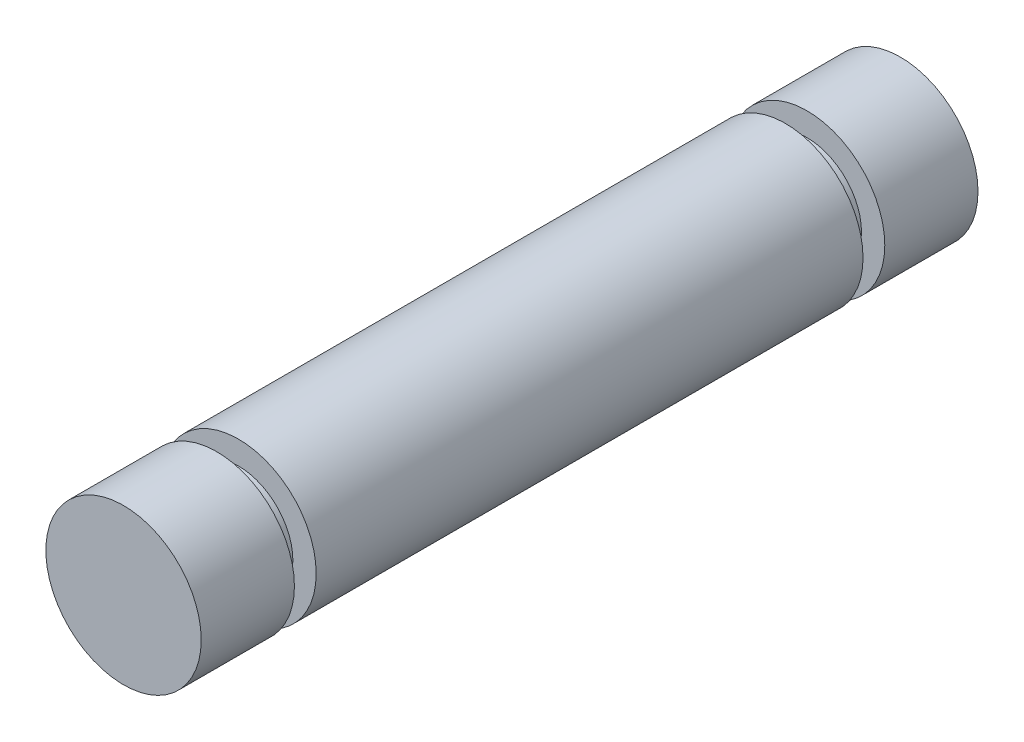
SolidWorks part; units mm, degrees
ref_plane "Front Plane" through (0, 0, 0) normal (0, 0, 1) x (1, 0, 0)
ref_plane "Top Plane" through (0, 0, 0) normal (0, 1, 0) x (1, 0, 0)
ref_plane "Right Plane" through (0, 0, 0) normal (1, 0, 0) x (0, 0, -1)
sketch "Sketch1" plane through (0, 0, 0) normal (0, 0, 1) x (1, 0, 0)
  circle A0 centre (0, 0) radius 3.175
  dimension "D1" = 6.35
extrude "Boss-Extrude1" add sketch "Sketch1" along normal mid plane 31.75
sketch "Sketch2" plane through (0, 0, 0) normal (0, 1, 0) x (1, 0, 0)
  line L0 (3.175, -15.875) -> (3.175, 15.875) construction
  line L1 (3.175, 12.065) -> (2.2225, 12.065)
  line L2 (3.175, 12.065) -> (3.175, 11.176)
  line L3 (3.175, 11.176) -> (2.2225, 11.176)
  line L4 (2.2225, 12.065) -> (2.2225, 11.176)
  line L5 (3.175, 15.875) -> (-3.175, 15.875) construction
  line L6 (3.175, -11.176) -> (2.2225, -11.176)
  line L7 (3.175, -11.176) -> (3.175, -12.065)
  line L8 (3.175, -12.065) -> (2.2225, -12.065)
  line L9 (2.2225, -11.176) -> (2.2225, -12.065)
  line L10 (-3.175, -15.875) -> (3.175, -15.875) construction
  point P10 (2.2225, 11.6205)
  dimension "D1" = 0.9525
  dimension "D2" = 0.9525
  dimension "D3" = 0.889
  dimension "D4" = 0.889
  dimension "D5" = 3.81
  dimension "D6" = 3.81
ref_axis "Axis1" through (0, 0, 15.875) along (0, 0, -1)
revolve "Cut-Revolve1" cut sketch "Sketch2" angle 360 about axis through (0, 0, 15.875) along (0, 0, -1)
